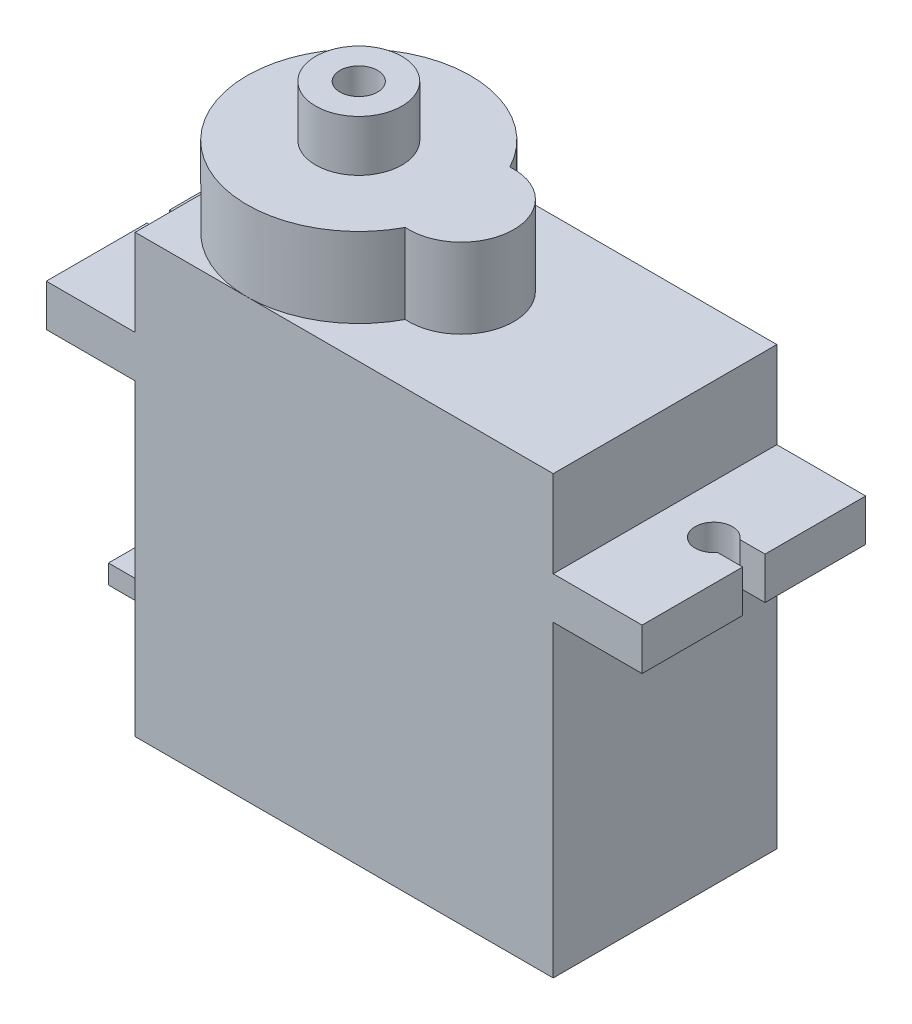
SolidWorks part; units mm, degrees
ref_plane "Front Plane" through (0, 0, 0) normal (0, 0, 1) x (1, 0, 0)
ref_plane "Top Plane" through (0, 0, 0) normal (0, 1, 0) x (1, 0, 0)
ref_plane "Right Plane" through (0, 0, 0) normal (1, 0, 0) x (0, 0, -1)
sketch "Sketch1" plane through (0, 0, 0) normal (0, 1, 0) x (1, 0, 0)
  line L1 (0, 0) -> (22.7711, 0)
  line L2 (0, 0) -> (0, 12.18)
  line L3 (0, 12.18) -> (22.7711, 12.18)
  line L4 (22.7711, 0) -> (22.7711, 12.18)
  dimension "D1" = 12.18
  dimension "D2" = 22.7711
extrude "Boss-Extrude1" add sketch "Sketch1" along normal blind 23.79
ref_plane "Plane1" through (0, 19.0656, 0) normal (0, 1, 0) x (1, 0, 0)
sketch "Sketch3" plane through (0, 19.0656, 0) normal (0, 1, 0) x (1, 0, 0)
  line L0 (22.7711, 12.18) -> (0, 12.18) construction
  line L1 (-4.8387, 0) -> (27.6098, 0)
  line L2 (-4.8387, 0) -> (-4.8387, 12.18)
  line L3 (-4.8387, 12.18) -> (27.6098, 12.18)
  line L4 (27.6098, 0) -> (27.6098, 12.18)
  line L5 (0, 0) -> (22.7711, 0) construction
  point P6 (11.3856, 0)
  point P9 (11.3856, 0)
  dimension "D1" = 32.4485
extrude "Boss-Extrude2" add sketch "Sketch3" against normal blind 2.286
sketch "Sketch4" plane through (0, 19.0656, 0) normal (0, 1, 0) x (1, 0, 0)
  line L0 (-3.4671, 6.6996) -> (-3.4671, 5.4804) construction
  line L1 (-4.8387, 6.6996) -> (-3.4671, 6.6996)
  line L2 (-4.8387, 12.18) -> (-4.8387, 0) construction
  line L3 (-3.4671, 5.4804) -> (-4.8387, 5.4804)
  line L4 (-1.6383, 6.09) -> (-1.6383, 8.3545) construction
  line L5 (11.3856, 12.18) -> (11.3856, 0) construction
  line L6 (22.7711, 12.18) -> (0, 12.18) construction
  line L7 (0, 0) -> (22.7711, 0) construction
  line L8 (24.4094, 6.09) -> (24.4094, 8.3545) construction
  line L9 (26.2382, 6.6996) -> (26.2382, 5.4804) construction
  line L10 (26.2382, 5.4804) -> (27.6098, 5.4804)
  line L11 (27.6098, 6.6996) -> (26.2382, 6.6996)
  line L12 (-4.8387, 6.6996) -> (-4.8387, 5.4804)
  line L13 (27.6098, 6.6996) -> (27.6098, 5.4804)
  arc A0 (-3.4671, 6.6996) -> (-3.4671, 5.4804) centre (-2.6543, 6.09) cw
  arc A1 (26.2382, 6.6996) -> (26.2382, 5.4804) centre (25.4254, 6.09) ccw
  point P6 (-3.4671, 6.09)
  point P8 (-4.8387, 6.09)
  dimension "D1" = 1.016
  dimension "D2" = 3.2004
  dimension "D3" = 1.2192
extrude "Cut-Extrude1" cut sketch "Sketch4" against normal through all
sketch "Sketch5" plane through (0, 23.79, 0) normal (0, 1, 0) x (1, 0, 0)
  line L0 (22.7711, 12.18) -> (0, 12.18) construction
  line L1 (0, 12.18) -> (0, 0) construction
  line L2 (0, 0) -> (22.7711, 0) construction
  line L3 (14.5288, 6.09) -> (14.5288, 9.2952) construction
  arc A0 (11.4717, 8.9405) -> (11.4717, 3.2395) centre (6.09, 6.09) ccw
  arc A1 (11.4717, 3.2395) -> (11.4717, 8.9405) centre (11.6713, 6.09) ccw
  dimension "D1" = 14.5288
  dimension "D2" = 5.715
extrude "Boss-Extrude3" add sketch "Sketch5" along normal blind 4.3434
sketch "Sketch6" plane through (0, 28.1334, 0) normal (0, 1, 0) x (1, 0, 0)
  circle A0 centre (6.09, 6.09) radius 2.3495
  arc A1 (11.4717, 8.9405) -> (11.4717, 3.2395) centre (6.09, 6.09) ccw construction
  dimension "D1" = 4.699
extrude "Boss-Extrude4" add sketch "Sketch6" along normal blind 2.7813 contours A0
sketch "Sketch7" plane through (0, 0, 0) normal (-1, 0, 0) x (0, 0, 1)
  line L0 (-12.18, 0) -> (0, 0) construction
  line L1 (-7.5378, 1.78) -> (-4.6422, 1.78)
  line L2 (-7.5378, 1.78) -> (-7.5378, 2.8214)
  line L3 (-7.5378, 2.8214) -> (-4.6422, 2.8214)
  line L4 (-4.6422, 1.78) -> (-4.6422, 2.8214)
  point P4 (-6.09, 1.78)
  point P7 (-6.09, 0)
  dimension "D1" = 1.0414
  dimension "D2" = 2.8956
  dimension "D3" = 1.78
extrude "Boss-Extrude5" add sketch "Sketch7" along normal blind 6.096
ref_axis "Axis1" through (6.09, 30.9147, -6.09) along (0, -1, 0)
ref_plane "Plane2" through (6.09, 0, 0) normal (-1, 0, 0) x (0, 0, 1)
sketch "Sketch8" plane through (0, 28.1334, 0) normal (0, 1, 0) x (1, 0, 0)
  circle A0 centre (6.09, 6.09) radius 3.556
  dimension "D1" = 7.112
extrude "Boss-Extrude6" [suppressed] add sketch "Sketch8" along normal blind 4.4577
sketch "Sketch9" [suppressed] plane through (0, 31.9532, 0) normal (0, 1, 0) x (1, 0, 0)
  line L0 (2.5019, 6.0579) -> (3.8735, 18.5674)
  line L1 (3.8735, 18.5674) -> (8.2423, 18.5674)
  line L2 (8.2423, 18.5674) -> (9.6139, 6.0579)
  line L3 (6.0579, 6.0579) -> (6.0579, 18.5674) construction
  line L4 (2.5019, 6.0579) -> (9.6139, 6.0579)
  line L5 (8.9281, 12.3127) -> (6.0579, 12.3127) construction
  line L6 (6.0579, 12.3127) -> (3.1877, 12.3127) construction
  circle A0 centre (6.0579, 6.0579) radius 3.556 construction
  point P10 (6.0579, 18.5674)
  point P18 (6.0579, 2.5019)
  dimension "D1" = 4.3688
  dimension "D2" = 16.0655
extrude "Boss-Extrude7" [suppressed] add sketch "Sketch9" against normal blind 1.651
sketch "Sketch11" [suppressed] plane through (0, 31.9532, 0) normal (0, 1, 0) x (1, 0, 0)
  circle A0 centre (6.0579, 6.0579) radius 2.4257
  arc A1 (2.5864, 6.8284) -> (9.5294, 6.8284) centre (6.0579, 6.0579) ccw construction
  dimension "D1" = 4.8514
extrude "Cut-Extrude2" [suppressed] cut sketch "Sketch11" against normal blind 2.54
sketch "Sketch12" [suppressed] plane through (0, 29.4132, 0) normal (0, 1, 0) x (1, 0, 0)
  circle A0 centre (6.0579, 6.0579) radius 1.2001
  dimension "D1" = 2.4003
extrude "Cut-Extrude3" [suppressed] cut sketch "Sketch12" against normal up to surface (1.9177 mm away)
hole_wizard "M2.5x0.45 Tapped Hole1" positions "Sketch14" profile "Sketch15" tap size "M2.5x0.45" standard "ANSI Metric"
sketch "Sketch14" plane through (0, 30.9147, 0) normal (0, 1, 0) x (1, 0, 0)
  point P0 (6.09, 6.09)
sketch "Sketch15" plane through (6.09, 30.9147, -6.09) normal (1, 0, 0) x (0, 0, 1)
  line L0 (0, 0) -> (0, 4.6159)
  line L1 (0, 4.6159) -> (1.025, 4)
  line L2 (1.025, 4) -> (1.025, 0)
  line L5 (1.025, 0) -> (0, 0)
  line L10 (0, 4.6159) -> (-1.025, 4) construction
  line L11 (0, -6.35) -> (0, 107.95) construction
  dimension "Tap Drill Dia." = 2.05
  dimension "Tap Drill Depth" = 4
  dimension "Drill Angle" = 118
cosmetic thread "Hole Thread1" parameters "D1"=4, "D2"=2.5
ref_plane "Plane3" through (0, 26.2988, 0) normal (0, 1, 0) x (1, 0, 0)
ref_point "Point1"
